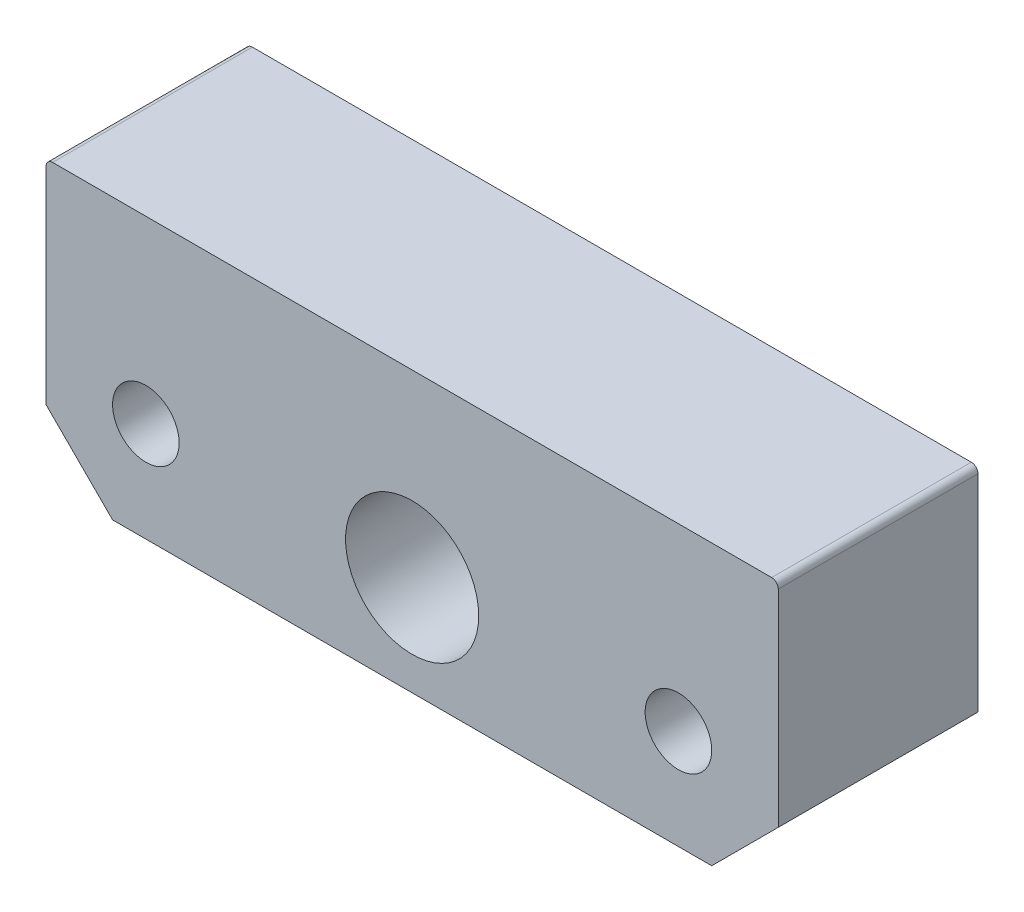
SolidWorks part; units mm, degrees
ref_plane "Alzado" through (0, 0, 0) normal (0, 0, 1) x (1, 0, 0)
ref_plane "Planta" through (0, 0, 0) normal (0, 1, 0) x (1, 0, 0)
ref_plane "Vista lateral" through (0, 0, 0) normal (1, 0, 0) x (0, 0, -1)
sketch "Croquis1" plane through (0, 0, 0) normal (0, 0, 1) x (1, 0, 0)
  line L1 (-55, -21) -> (55, -21)
  line L2 (-55, -21) -> (-55, 21)
  line L3 (-55, 21) -> (55, 21)
  line L4 (55, -21) -> (55, 21)
  line L5 (-55, -21) -> (55, 21) construction
  line L6 (-55, 21) -> (55, -21) construction
  point P0 (0, 0)
  dimension "D1" = 42
  dimension "D2" = 110
extrude "Saliente-Extruir1" add sketch "Croquis1" along normal blind 30
chamfer "Chaflán1" distance 10 angle 45 2 edges at (-55, -21, 15) (55, -21, 15)
fillet "Redondeo1" radius 1 2 edges at (-55, 21, 15) (55, 21, 15)
sketch "Croquis2" plane through (0, 0, 30) normal (0, 0, 1) x (1, 0, 0)
  line L0 (-40, -6) -> (40, -6) construction
  line L1 (54, 21) -> (-54, 21) construction
  circle A0 centre (-40, -6) radius 5
  circle A1 centre (40, -6) radius 5
  circle A2 centre (0, -6) radius 10
  point P4 (0, -6)
  dimension "D2" = 10
  dimension "D3" = 20
  dimension "D1" = 80
  dimension "D4" = 27
extrude "Cortar-Extruir1" cut sketch "Croquis2" against normal blind 30
